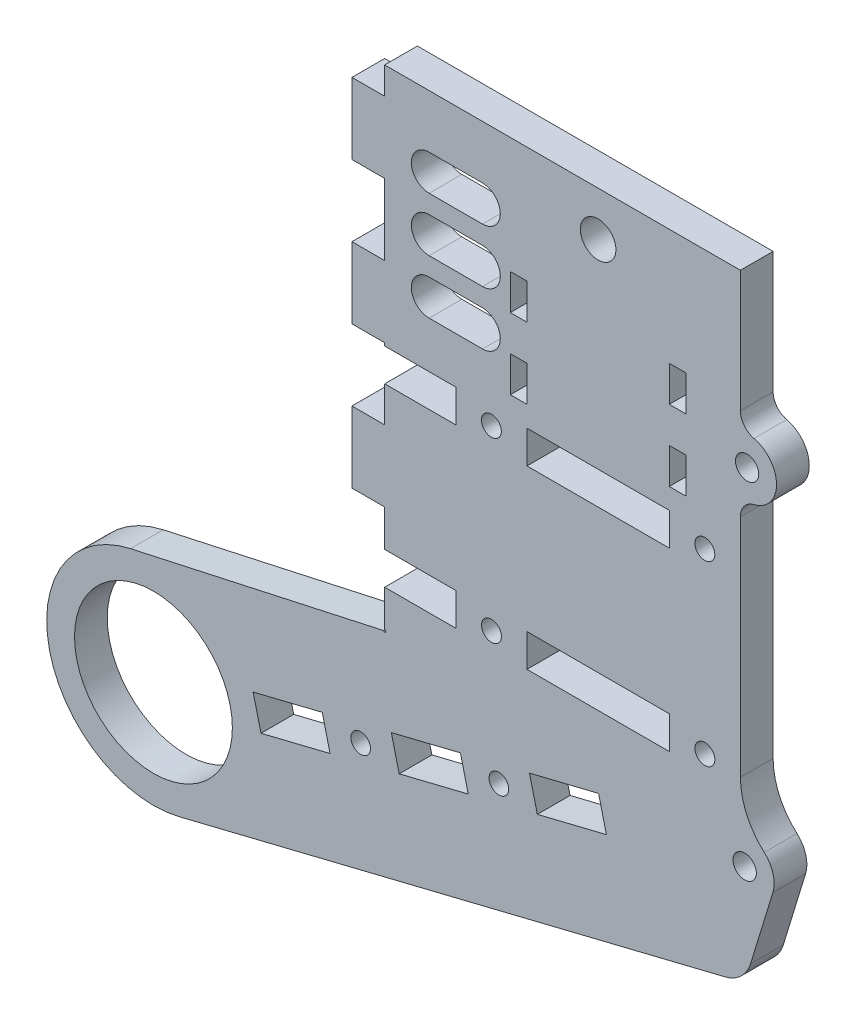
SolidWorks part; units mm, degrees
ref_plane "Front Plane" through (0, 0, 0) normal (0, 0, 1) x (1, 0, 0)
ref_plane "Top Plane" through (0, 0, 0) normal (0, 1, 0) x (1, 0, 0)
ref_plane "Right Plane" through (0, 0, 0) normal (1, 0, 0) x (0, 0, -1)
sketch "Sketch1" plane through (0, 0, 0) normal (0, 0, 1) x (1, 0, 0)
  line L0 (0, 0) -> (0, -12.7) construction
  line L1 (-5.842, 12.7) -> (0, 12.7)
  line L3 (-5.842, 0) -> (0, 0)
  line L4 (0, 0) -> (0, -12.7)
  line L5 (-53.8955, 12.7) -> (-53.8955, -55.5432) construction
  line L6 (0, -50.8) -> (0, -57.3499)
  line L7 (-5.842, -12.7) -> (0, -12.7)
  line L9 (0, -25.908) -> (63.5, -25.908) construction
  line L10 (0, 0) -> (0, -12.7)
  line L11 (0, -31.75) -> (0, -38.1) construction
  line L12 (12.7, -28.702) -> (25.4, -28.702) construction
  line L13 (-5.842, -38.1) -> (0, -38.1)
  line L15 (-5.842, -50.8) -> (0, -50.8)
  line L16 (12.716, -60.3979) -> (25.416, -60.3979) construction
  line L17 (0, -31.75) -> (0, -38.1)
  line L18 (0, -25.908) -> (12.7, -25.908)
  line L19 (50.8, -63.1919) -> (63.5, -63.1919)
  line L20 (0, -31.75) -> (12.7, -31.75)
  line L21 (12.7, -25.908) -> (12.7, -31.75)
  line L22 (0, 17.5501) -> (63.5, 17.5501)
  line L23 (0, 17.5501) -> (0, 12.7)
  line L24 (12.7, -63.1919) -> (25.4, -63.1919)
  line L25 (63.5, 17.5501) -> (63.5, -63.1919)
  line L26 (0, -57.3499) -> (12.7, -57.3499)
  line L27 (25.4, -25.908) -> (50.8, -25.908)
  line L28 (25.4, -25.908) -> (25.4, -31.75)
  line L29 (12.7, -57.3499) -> (12.7, -63.1919)
  line L30 (25.4, -31.75) -> (50.8, -31.75)
  line L31 (50.8, -25.908) -> (50.8, -31.75)
  line L32 (25.4, -57.3499) -> (50.8, -57.3499)
  line L33 (25.4, -57.3499) -> (25.4, -63.1919)
  line L34 (-5.842, -25.4) -> (0, -25.4)
  line L35 (50.8, -57.3499) -> (50.8, -63.1919)
  line L36 (0, -25.4) -> (0, -25.908)
  line L37 (50.8, -28.702) -> (63.5, -28.702) construction
  line L38 (50.816, -60.3979) -> (63.5, -60.3979) construction
  line L40 (22.114, -63.4459) -> (16.018, -63.4459) construction
  line L41 (22.114, -63.4459) -> (22.114, -57.3499) construction
  line L42 (22.114, -57.3499) -> (16.018, -57.3499) construction
  line L43 (16.018, -63.4459) -> (16.018, -57.3499) construction
  line L44 (22.114, -63.4459) -> (16.018, -57.3499) construction
  line L45 (22.114, -57.3499) -> (16.018, -63.4459) construction
  line L46 (22.098, -25.654) -> (16.002, -25.654) construction
  line L47 (22.098, -25.654) -> (22.098, -31.75) construction
  line L48 (22.098, -31.75) -> (16.002, -31.75) construction
  line L49 (16.002, -25.654) -> (16.002, -31.75) construction
  line L50 (22.098, -25.654) -> (16.002, -31.75) construction
  line L51 (22.098, -31.75) -> (16.002, -25.654) construction
  line L55 (-5.842, 12.7) -> (-5.842, -50.8)
  circle A0 centre (19.05, -28.702) radius 1.778
  circle A1 centre (19.066, -60.3979) radius 1.778
  circle A2 centre (57.15, -28.702) radius 1.778
  circle A3 centre (57.158, -60.3979) radius 1.778
  dimension "D20" = 3.556
  dimension "D21" = 3.556
  dimension "D23" = 3.556
  dimension "D24" = 3.556
  dimension "D2" = 53.8955
  dimension "D3" = 0.508
  dimension "D4" = 5.842
  dimension "D5" = 12.7
  dimension "D6" = 4.8501
  dimension "D7" = 6.5499
  dimension "D8" = 12.7
  dimension "D9" = 5.842
  dimension "D10" = 5.842
  dimension "D11" = 25.4
  dimension "D12" = 12.7
  dimension "D13" = 5.842
  dimension "D14" = 25.4
  dimension "D15" = 12.7
  dimension "D16" = 12.7
  dimension "D18" = 6.35
  dimension "D19" = 12.7
  dimension "D22" = 63.5
  dimension "D25" = 6.096
  dimension "D26" = 6.096
  dimension "D27" = 3.048
  dimension "D28" = 6.096
  dimension "D29" = 6.096
  dimension "D30" = 5.842
extrude "Boss-Extrude1" add sketch "Sketch1" along normal blind 5.842 contours L32 L35 L19 L25 L22 L23 L1 L3 L4 L7 L18 L21 L20 L17 L13 L15 L6 L26 L29 L24 L33 L31 region at (30.4992, -20.4826, 0)
sketch "Sketch2" plane through (0, 0, 5.842) normal (0, 0, 1) x (1, 0, 0)
  line L0 (63.5, -63.1919) -> (0, -63.1919)
  line L1 (63.5, -69.9498) -> (0, -69.9498)
  line L2 (0, -69.9498) -> (0, -63.1919)
  line L3 (63.5, -69.9498) -> (63.5, -63.1919)
  dimension "D1" = 6.7579
extrude "Boss-Extrude2" add sketch "Sketch2" against normal up to surface (5.842 mm away) up to face at (58.936, -60.3979, 0)
fillet "Fillet1" radius 3.175 1 edges at (63.5, -69.9498, 2.921)
sketch "Sketch3" plane through (0, 0, 5.842) normal (0, 0, 1) x (1, 0, 0)
  line L0 (38.1, -31.75) -> (38.1, -57.3499) construction
  line L1 (25.4, -31.75) -> (50.8, -31.75) construction
  line L2 (25.4, -57.3499) -> (50.8, -57.3499) construction
  line L3 (38.1, -44.5499) -> (-5.842, -44.45) construction
  line L4 (-5.842, -38.1) -> (-5.842, -50.8) construction
  line L5 (49.2125, -38.1855) -> (39.6875, -50.8855) construction
  line L6 (26.9875, -50.8855) -> (36.5125, -50.8855)
  line L7 (26.9875, -50.8855) -> (26.9875, -38.1855)
  line L8 (26.9875, -38.1855) -> (36.5125, -38.1855)
  line L9 (36.5125, -50.8855) -> (36.5125, -38.1855)
  line L10 (26.9875, -50.8855) -> (36.5125, -38.1855) construction
  line L11 (26.9875, -38.1855) -> (36.5125, -50.8855) construction
  line L12 (49.2125, -50.8855) -> (39.6875, -38.1855) construction
  line L13 (39.6875, -50.8855) -> (39.6875, -38.1855)
  line L14 (49.2125, -38.1855) -> (39.6875, -38.1855)
  line L15 (49.2125, -50.8855) -> (49.2125, -38.1855)
  line L16 (49.2125, -50.8855) -> (39.6875, -50.8855)
  point P10 (31.75, -44.5355)
  point P19 (44.45, -44.5355)
  dimension "D1" = 9.525
  dimension "D2" = 12.7
  dimension "D3" = 6.35
extrude "Cut-Extrude1" [suppressed] cut sketch "Sketch3" against normal through all
fillet "Fillet2" [suppressed] radius 3.175
sketch "Sketch4" plane through (0, 0, 5.842) normal (0, 0, 1) x (1, 0, 0)
  line L0 (38.1, -25.908) -> (38.1, 17.5501) construction
  line L1 (25.4, -25.908) -> (50.8, -25.908) construction
  line L2 (0, 17.5501) -> (63.5, 17.5501) construction
  line L3 (0, -12.7) -> (63.5, -12.7) construction
  line L4 (50.8, -25.3124) -> (25.4, -25.3124) construction
  line L5 (50.8, -25.3124) -> (50.8, 0.0876) construction
  line L6 (50.8, 0.0876) -> (25.4, 0.0876) construction
  line L7 (25.4, -25.3124) -> (25.4, 0.0876) construction
  line L8 (50.8, -25.3124) -> (25.4, 0.0876) construction
  line L9 (50.8, 0.0876) -> (25.4, -25.3124) construction
  line L10 (63.5, 17.5501) -> (63.5, -66.7748) construction
  line L11 (22.425, -15.875) -> (25.4, -22.225) construction
  line L12 (22.425, -3.175) -> (25.4, -3.175)
  line L13 (22.425, -3.175) -> (22.425, -9.525)
  line L14 (22.425, -9.525) -> (25.4, -9.525)
  line L15 (25.4, -3.175) -> (25.4, -9.525)
  line L16 (22.425, -3.175) -> (25.4, -9.525) construction
  line L17 (22.425, -9.525) -> (25.4, -3.175) construction
  line L18 (22.425, -22.225) -> (25.4, -15.875) construction
  line L19 (25.4, -22.225) -> (25.4, -15.875)
  line L20 (22.425, -15.875) -> (25.4, -15.875)
  line L21 (22.425, -22.225) -> (22.425, -15.875)
  line L22 (22.425, -22.225) -> (25.4, -22.225)
  line L23 (53.775, -22.225) -> (50.8, -15.875) construction
  line L24 (53.775, -9.525) -> (50.8, -3.175) construction
  line L25 (53.775, -3.175) -> (50.8, -9.525) construction
  line L26 (53.775, -15.875) -> (50.8, -22.225) construction
  line L27 (53.775, -22.225) -> (50.8, -22.225)
  line L28 (53.775, -22.225) -> (53.775, -15.875)
  line L29 (53.775, -15.875) -> (50.8, -15.875)
  line L30 (50.8, -22.225) -> (50.8, -15.875)
  line L31 (50.8, -3.175) -> (50.8, -9.525)
  line L32 (53.775, -9.525) -> (50.8, -9.525)
  line L33 (53.775, -3.175) -> (53.775, -9.525)
  line L34 (53.775, -3.175) -> (50.8, -3.175)
  circle A0 centre (38.1, 9.6126) radius 3.175
  point P8 (38.1, -12.6124)
  point P18 (23.9125, -6.35)
  point P27 (23.9125, -19.05)
  point P36 (52.2875, -19.05)
  point P37 (52.2875, -6.35)
  dimension "D1" = 6.35
  dimension "D2" = 7.9375
  dimension "D3" = 25.4
  dimension "D4" = 25.4
  dimension "D5" = 9.525
  dimension "D6" = 2.975
  dimension "D7" = 6.35
  dimension "D8" = 3.175
extrude "Cut-Extrude2" cut sketch "Sketch4" against normal through all
sketch "Sketch5" plane through (0, 0, 5.842) normal (0, 0, 1) x (1, 0, 0)
  line L0 (0, 17.5501) -> (63.5, 17.5501) construction
  line L2 (0, -6.35) -> (22.225, -6.35) construction
  line L3 (0, 0) -> (0, -12.7) construction
  line L4 (7.9375, -4.8019) -> (17.4625, -4.8019) construction
  line L6 (7.9375, 4.8501) -> (17.4625, 4.8501) construction
  line L7 (7.9375, 8.0251) -> (17.4625, 8.0251)
  line L8 (7.9375, 1.6751) -> (17.4625, 1.6751)
  line L9 (7.9375, -1.6269) -> (17.4625, -1.6269)
  line L10 (7.9375, -7.9769) -> (17.4625, -7.9769)
  line L11 (7.9375, -14.4539) -> (17.4625, -14.4539) construction
  line L12 (7.9375, -11.2789) -> (17.4625, -11.2789)
  line L13 (7.9375, -17.6289) -> (17.4625, -17.6289)
  arc A1 (7.9375, 8.0251) -> (7.9375, 1.6751) centre (7.9375, 4.8501) ccw
  arc A2 (17.4625, 1.6751) -> (17.4625, 8.0251) centre (17.4625, 4.8501) ccw
  arc A3 (7.9375, -1.6269) -> (7.9375, -7.9769) centre (7.9375, -4.8019) ccw
  arc A4 (17.4625, -7.9769) -> (17.4625, -1.6269) centre (17.4625, -4.8019) ccw
  arc A5 (7.9375, -11.2789) -> (7.9375, -17.6289) centre (7.9375, -14.4539) ccw
  arc A6 (17.4625, -17.6289) -> (17.4625, -11.2789) centre (17.4625, -14.4539) ccw
  point P5 (12.7, -4.8019)
  point P17 (12.7, 4.8501)
  point P24 (12.7, -14.4539)
  dimension "D2" = 3.175
  dimension "D1" = 9.525
  dimension "D3" = 12.7
  dimension "D5" = 3
  dimension "D4" = 9.525
sketch "Sketch6" plane through (0, 0, 5.842) normal (0, 0, 1) x (1, 0, 0)
  line L0 (63.5, -7.8499) -> (139.7, 17.5501)
  line L1 (63.5, 17.5501) -> (63.5, -66.7748) construction
  line L2 (63.5, -7.8499) -> (63.5, 17.5501)
  line L3 (139.7, 17.5501) -> (63.5, 17.5501)
  line L4 (69.85, 0.9603) -> (100.5695, 11.2001)
  line L5 (100.5695, 11.2001) -> (69.85, 11.2001)
  line L6 (69.85, 0.9603) -> (69.85, 11.2001)
  dimension "D1" = 25.4
  dimension "D2" = 76.2
  dimension "D3" = 6.35
extrude "Boss-Extrude3" [suppressed] add sketch "Sketch6" against normal up to surface (5.842 mm away) up to face at (52.2875, -6.35, 0)
fillet "Fillet9" [suppressed] radius 12.7
fillet "Fillet10" [suppressed] radius 0.7937
fillet "Fillet11" [suppressed] radius 1.5875
extrude "Cut-Extrude3" cut sketch "Sketch5" against normal through all
sketch "Sketch7" plane through (0, 0, 5.842) normal (0, 0, 1) x (1, 0, 0)
  line L0 (63.5, 17.5501) -> (63.5, -66.7748) construction
  line L1 (64.262, -74.2322) -> (60.0456, -74.2322) construction
  line L2 (64.262, -74.2322) -> (60.5442, -77.95) construction
  line L3 (60.5442, -77.95) -> (55.2185, -69.9498)
  line L4 (0, -69.9498) -> (60.325, -69.9498) construction
  line L5 (55.2185, -69.9498) -> (60.325, -69.9498)
  line L6 (63.5, -66.7748) -> (67.6153, -70.1825)
  circle A0 centre (64.262, -74.2322) radius 2.0828
  arc A1 (60.5442, -77.95) -> (67.6153, -70.1825) centre (64.262, -74.2322) ccw
  arc A2 (60.325, -69.9498) -> (63.5, -66.7748) centre (60.325, -66.7748) ccw construction
  arc A3 (60.325, -69.9498) -> (63.5, -66.7748) centre (60.325, -66.7748) ccw
  circle A5 centre (64.262, -74.2322) radius 5.2578 construction
  point P7 (68.2942, -71.7977)
  dimension "D1" = 4.1656
  dimension "D2" = 0.762
  dimension "D4" = 45
  dimension "D3" = 3.175
extrude "Boss-Extrude4" add sketch "Sketch7" against normal up to surface (5.842 mm away) up to face at (12.7, -14.4539, 0)
fillet "Fillet12" radius 12.7 2 edges at (55.2185, -69.9498, 2.921) (63.5, -66.7748, 2.921)
sketch "Sketch8" plane through (0, 0, 5.842) normal (0, 0, 1) x (1, 0, 0)
  line L0 (63.5, 17.5501) -> (63.5, -60.817) construction
  line L1 (0, -69.9498) -> (48.4162, -69.9498) construction
  line L2 (64.6935, -17.6103) -> (63.5, -17.6103)
  line L3 (63.5, -17.6103) -> (63.5, -17.4731)
  line L4 (64.6935, -7.0947) -> (63.5, -7.0947)
  line L5 (63.5, -7.0947) -> (63.5, -7.232)
  circle A0 centre (64.6935, -12.3525) radius 2.0828
  arc A1 (64.6935, -17.6103) -> (64.6935, -7.0947) centre (64.6935, -12.3525) ccw
  arc A2 (63.5, -7.232) -> (63.5, -17.4731) centre (64.6935, -12.3525) ccw
  circle A3 centre (64.6935, -12.3525) radius 5.2578 construction
  point P10 (69.9513, -12.3525)
  dimension "D1" = 4.1656
  dimension "D2" = 1.1935
  dimension "D3" = 57.5973
  dimension "D4" = 3.175
extrude "Boss-Extrude5" add sketch "Sketch8" against normal up to surface (5.842 mm away) up to face at (13.6459, -34.9045, 0)
fillet "Fillet13" radius 3.175 2 edges at (63.5, -17.6103, 2.921) (63.5, -7.0947, 2.921)
sketch "Sketch9" plane through (0, 0, 5.842) normal (0, 0, 1) x (1, 0, 0)
  circle A0 centre (64.6935, -12.3525) radius 2.0828
extrude "Cut-Extrude4" cut sketch "Sketch9" against normal through all
sketch "Sketch10" [suppressed] plane through (0, 0, 5.842) normal (0, 0, 1) x (1, 0, 0)
  line L0 (0, -88.2063) -> (0, -146.1498)
  line L1 (38.1, -69.9498) -> (3.175, -171.5498)
  line L2 (0, -69.9498) -> (48.4162, -69.9498) construction
  line L3 (3.175, -171.5498) -> (0, -171.5498)
  line L4 (38.1, -69.9498) -> (0, -69.9498)
  line L5 (9.525, -79.4748) -> (9.525, -123.7766)
  line L6 (9.525, -123.7766) -> (9.525, -123.7766)
  line L7 (24.7537, -79.4748) -> (9.525, -123.7766)
  line L8 (24.7537, -79.4748) -> (9.525, -79.4748)
  line L9 (0, -69.6643) -> (-5.842, -69.6643)
  line L10 (0, -63.1919) -> (0, -69.9498) construction
  line L11 (-5.842, -69.6643) -> (-5.842, -82.3643)
  line L12 (0, -69.9498) -> (0, -69.6643)
  line L13 (0, -69.9498) -> (0, -171.5498) construction
  line L14 (-5.842, -82.3643) -> (0, -88.2063)
  line L15 (0, -171.5498) -> (-9.525, -171.5498)
  line L16 (-9.525, -171.5498) -> (-9.525, -158.8498)
  line L17 (-9.525, -158.8498) -> (0, -146.1498)
  line L18 (-9.525, -165.1998) -> (5.3578, -165.1998) construction
  circle A0 centre (9.525, -130.1266) radius 2.0828
  circle A1 centre (-2.0836, -165.1998) radius 2.0828
  dimension "D5" = 4.1656
  dimension "D13" = 4.1656
  dimension "D1" = 101.6
  dimension "D2" = 3.175
  dimension "D3" = 38.1
  dimension "D6" = 6.35
  dimension "D7" = 5.842
  dimension "D8" = 0.2855
  dimension "D9" = 12.7
  dimension "D10" = 12.7
  dimension "D11" = 9.525
  dimension "D12" = 25.4
  dimension "D4" = 9.525
extrude "Boss-Extrude6" [suppressed] add sketch "Sketch10" against normal up to surface (5.842 mm away) up to face at (66.7763, -12.3525, 0)
fillet "Fillet14" [suppressed] radius 2.54
fillet "Fillet15" [suppressed] radius 6.35
fillet "Fillet16" [suppressed] radius 6.35
sketch "Sketch11" [suppressed] plane through (0, 0, 5.842) normal (0, 0, 1) x (1, 0, 0)
  line L0 (38.1, -25.908) -> (38.1, 17.5501) construction
  line L1 (25.4, -25.908) -> (50.8, -25.908) construction
  line L2 (0, 17.5501) -> (63.5, 17.5501) construction
  circle A0 centre (38.1, -4.1789) radius 9.525
extrude "Cut-Extrude5" [suppressed] cut sketch "Sketch11" against normal through all
sketch "Sketch12" plane through (0, 0, 0) normal (0, 0, -1) x (-1, 0, 0)
  line L0 (-48.4162, -69.9498) -> (0, -69.9498) construction
  line L1 (0, -69.9498) -> (66.4134, -69.9498) construction
  line L2 (0, -69.9498) -> (45.3638, -79.9188)
  line L3 (36.726, -117.0237) -> (-64.262, -92.19)
  line L4 (-64.262, -79.49) -> (-64.262, -92.19) construction
  line L5 (-64.262, -92.19) -> (-69.2894, -75.7716)
  line L6 (-60.5442, -77.95) -> (-58.9879, -75.6122) construction
  line L7 (-48.4162, -69.9498) -> (0, -69.9498)
  line L8 (-60.5442, -77.95) -> (-58.9879, -75.6122)
  circle A0 centre (41.275, -98.5248) radius 14.0875
  arc A1 (36.726, -117.0237) -> (45.3638, -79.9188) centre (41.275, -98.5248) ccw
  arc A2 (-67.7573, -70.3044) -> (-60.5442, -77.95) centre (-64.262, -74.2322) ccw construction
  arc A3 (-48.4162, -69.9498) -> (-58.9879, -75.6122) centre (-48.4162, -82.6498) ccw construction
  arc A4 (-48.4162, -69.9498) -> (-58.9879, -75.6122) centre (-48.4162, -82.6498) ccw
  arc A5 (-69.2894, -75.7716) -> (-60.5442, -77.95) centre (-64.262, -74.2322) ccw
  dimension "D1" = 28.175
  dimension "D4" = 38.1
  dimension "D2" = 28.575
  dimension "D3" = 41.275
  dimension "D5" = 12.7
extrude "Boss-Extrude7" add sketch "Sketch12" against normal up to surface (5.842 mm away) up to face at (66.7763, -12.3525, 5.842)
fillet "Fillet17" radius 6.35 1 edges at (64.262, -92.19, 2.921)
sketch "Sketch13" plane through (0, 0, 0) normal (0, 0, -1) x (-1, 0, 0)
  circle A0 centre (0, -69.9498) radius 0.1984
  dimension "D1" = 0.3969
extrude "Cut-Extrude6" cut sketch "Sketch13" against normal through all
sketch "Sketch14" plane through (0, 0, 0) normal (0, 0, -1) x (-1, 0, 0)
  line L0 (41.275, -98.5248) -> (-86.4701, -67.1113) construction
  line L1 (-60.7619, -93.0507) -> (36.726, -117.0237) construction
  line L2 (9.746, -93.7796) -> (22.0786, -96.8123)
  line L3 (9.746, -93.7796) -> (11.141, -88.1066)
  line L4 (22.0786, -96.8123) -> (23.4736, -91.1393)
  line L5 (11.141, -88.1066) -> (23.4736, -91.1393)
  line L6 (9.746, -93.7796) -> (23.4736, -91.1393) construction
  line L7 (22.0786, -96.8123) -> (11.141, -88.1066) construction
  line L8 (-13.5242, -82.0413) -> (-1.1916, -85.0739)
  line L9 (-2.5866, -90.7469) -> (-1.1916, -85.0739)
  line L10 (-14.9192, -87.7143) -> (-2.5866, -90.7469)
  line L11 (-14.9192, -87.7143) -> (-13.5242, -82.0413)
  line L12 (-38.1893, -75.9759) -> (-25.8567, -79.0086)
  line L13 (-27.2518, -84.6816) -> (-25.8567, -79.0086)
  line L14 (-39.5844, -81.6489) -> (-27.2518, -84.6816)
  line L15 (-39.5844, -81.6489) -> (-38.1893, -75.9759)
  circle A0 centre (4.2772, -89.4268) radius 1.7526
  circle A1 centre (-20.388, -83.3614) radius 1.7526
  point P6 (16.6098, -92.4595)
  dimension "D5" = 3.5052
  dimension "D1" = 12.7
  dimension "D2" = 5.842
  dimension "D3" = 25.4
  dimension "D6" = 12.7
  dimension "D7" = 2
extrude "Cut-Extrude7" cut sketch "Sketch14" against normal through all
